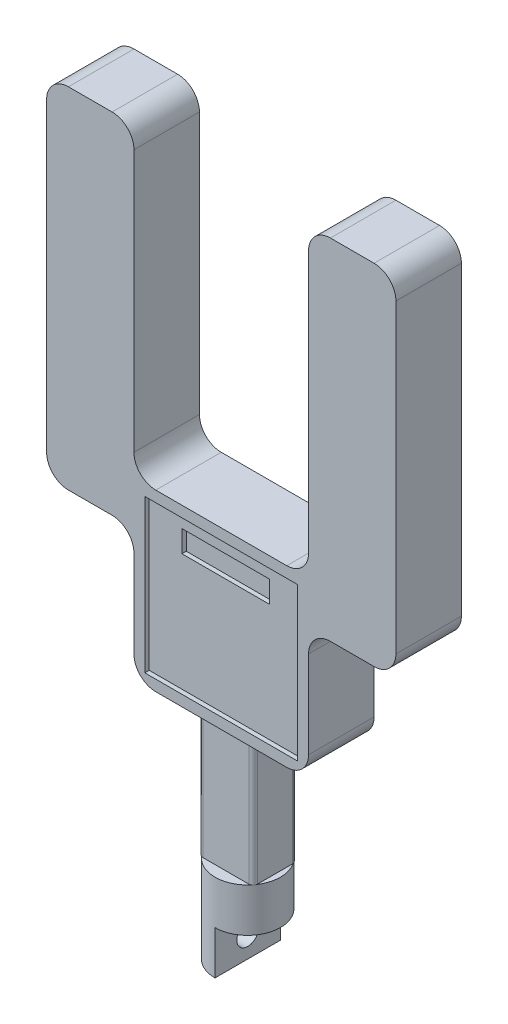
SolidWorks part; units mm, degrees
material "ABS"
ref_plane "Front Plane" through (0, 0, 0) normal (0, 0, 1) x (1, 0, 0)
ref_plane "Top Plane" through (0, 0, 0) normal (0, 1, 0) x (1, 0, 0)
ref_plane "Right Plane" through (0, 0, 0) normal (1, 0, 0) x (0, 0, -1)
sketch "Sketch1" plane through (0, 0, 0) normal (0, 0, 1) x (1, 0, 0)
  line L1 (0, 0) -> (101.6, 0)
  line L2 (0, 0) -> (0, 101.6)
  line L3 (0, 101.6) -> (101.6, 101.6)
  line L4 (101.6, 0) -> (101.6, 101.6)
  dimension "D1" = 101.6
  dimension "D2" = 101.6
extrude "Boss-Extrude1" add sketch "Sketch1" along normal blind 38.1
sketch "Sketch2" plane through (0, 0, 38.1) normal (0, 0, 1) x (1, 0, 0)
  line L0 (53.1956, 105.705) -> (53.1956, -2.2748) construction
  line L1 (0, 101.6) -> (0, 0) construction
  line L2 (25.4, 87.2922) -> (76.2, 87.2922)
  line L3 (25.4, 87.2922) -> (25.4, 74.5922)
  line L4 (25.4, 74.5922) -> (76.2, 74.5922)
  line L5 (76.2, 87.2922) -> (76.2, 74.5922)
  dimension "D1" = 12.7
  dimension "D2" = 50.8
  dimension "D4" = 25.4
extrude "Cut-Extrude1" cut sketch "Sketch2" against normal blind 5.08
sketch "Sketch3" plane through (0, 0, 38.1) normal (0, 0, 1) x (1, 0, 0)
  line L0 (0, 101.6) -> (0, 0) construction
  line L1 (6.35, 95.25) -> (95.25, 95.25)
  line L2 (6.35, 95.25) -> (6.35, 6.35)
  line L3 (6.35, 6.35) -> (95.25, 6.35)
  line L4 (95.25, 95.25) -> (95.25, 6.35)
  line L5 (101.6, 101.6) -> (0, 101.6) construction
  line L6 (101.6, 0) -> (101.6, 101.6) construction
  line L7 (0, 0) -> (101.6, 0) construction
  dimension "D1" = 6.35
  dimension "D2" = 6.35
  dimension "D3" = 6.35
  dimension "D4" = 6.35
extrude "Cut-Extrude2" cut sketch "Sketch3" against normal blind 2.54
sketch "Sketch4" plane through (0, 0, 0) normal (0, -1, 0) x (1, 0, 0)
  line L0 (-4.4429, 19.05) -> (107.6339, 19.05) construction
  line L1 (31.2661, 31.75) -> (63.0161, 31.75)
  line L2 (31.2661, 31.75) -> (31.2661, 6.35)
  line L3 (31.2661, 6.35) -> (63.0161, 6.35)
  line L4 (63.0161, 31.75) -> (63.0161, 6.35)
  line L5 (0, 38.1) -> (101.6, 38.1) construction
  dimension "D1" = 31.75
  dimension "D2" = 25.4
  dimension "D3" = 12.7
  dimension "D4" = 19.05
extrude "Boss-Extrude2" add sketch "Sketch4" along normal blind 76.2
sketch "Sketch6" plane through (0, -76.2, 0) normal (0, -1, 0) x (1, 0, 0)
  line L0 (47.1411, 31.75) -> (47.1411, 6.35) construction
  line L1 (63.0161, 31.75) -> (31.2661, 31.75) construction
  line L2 (31.2661, 6.35) -> (63.0161, 6.35) construction
  circle A0 centre (47.1411, 19.05) radius 19.05
  dimension "D1" = 38.1
extrude "Boss-Extrude3" add sketch "Sketch6" along normal blind 50.8
sketch "Sketch7" plane through (0, -127, 0) normal (0, -1, 0) x (1, 0, 0)
  line L0 (47.1411, 38.1) -> (47.1411, 0) construction
  line L2 (47.1411, 45.6861) -> (72.0041, 45.6861)
  line L3 (47.1411, 45.6861) -> (47.1411, -4.2311)
  line L4 (47.1411, -4.2311) -> (72.0041, -4.2311)
  line L5 (72.0041, 45.6861) -> (72.0041, -4.2311)
  circle A0 centre (47.1411, 19.05) radius 19.05 construction
extrude "Cut-Extrude3" cut sketch "Sketch7" against normal blind 25.4
sketch "Sketch8" plane through (0, 0, 0) normal (0, 0, -1) x (-1, 0, 0)
  line L0 (0, 101.6) -> (0, 0) construction
  line L1 (0, 76.2) -> (50.8, 76.2)
  line L2 (0, 76.2) -> (0, 279.4)
  line L3 (0, 279.4) -> (50.8, 279.4)
  line L4 (50.8, 76.2) -> (50.8, 279.4)
  line L5 (-101.6, 101.6) -> (0, 101.6) construction
  line L6 (-101.6, 0) -> (-101.6, 101.6) construction
  line L7 (-101.6, 76.2) -> (-152.4, 76.2)
  line L8 (-101.6, 76.2) -> (-101.6, 279.4)
  line L9 (-101.6, 279.4) -> (-152.4, 279.4)
  line L10 (-152.4, 76.2) -> (-152.4, 279.4)
  dimension "D1" = 203.2
  dimension "D2" = 50.8
  dimension "D3" = 25.4
  dimension "D4" = 50.8
extrude "Boss-Extrude4" add sketch "Sketch8" against normal up to surface (38.1 mm away) up to face at (50.8, 50.8, 38.1)
fillet "Fillet1" radius 12.7 12 edges at (101.6, 0, 19.05) (0, 0, 19.05) (152.4, 76.2, 19.05) (-50.8, 76.2, 19.05) (-50.8, 279.4, 19.05) (101.6, 279.4, 19.05) (152.4, 279.4, 19.05) (0, 279.4, 19.05)
sketch "Sketch9" plane through (47.1411, 0, 0) normal (1, 0, 0) x (0, 0, -1)
  line L0 (-38.1, -127) -> (0, -127) construction
  line L1 (0, -101.6) -> (0, -127) construction
  circle A0 centre (-19.05, -114.3) radius 6.35
  dimension "D1" = 12.7
  dimension "D2" = 12.7
  dimension "D3" = 19.05
extrude "Cut-Extrude4" cut sketch "Sketch9" against normal through all
fillet "Fillet2" radius 2.54 4 edges at (63.0161, -38.1, 6.35) (31.2661, -38.1, 6.35) (31.2661, -38.1, 31.75) (63.0161, -38.1, 31.75)
